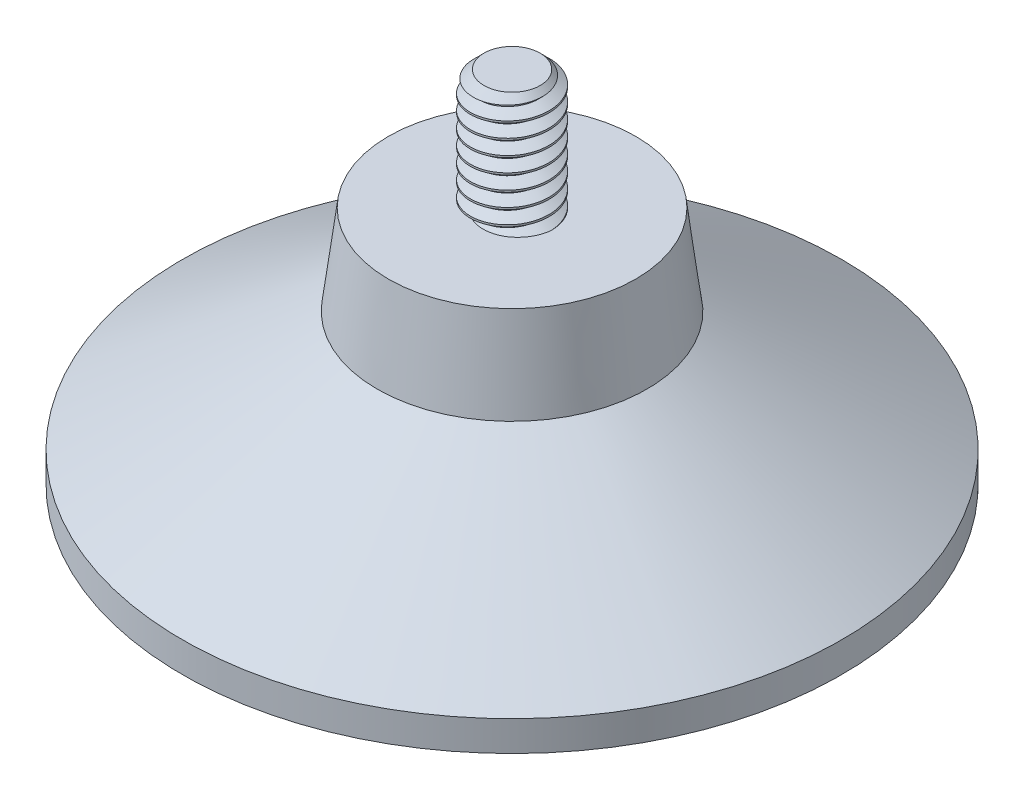
SolidWorks part; units mm, degrees
ref_plane "Front" through (0, 0, 0) normal (0, 0, 1) x (1, 0, 0)
ref_plane "Top" through (0, 0, 0) normal (0, 1, 0) x (1, 0, 0)
ref_plane "Right" through (0, 0, 0) normal (1, 0, 0) x (0, 0, -1)
sketch "Sketch1" plane through (0, 0, 0) normal (0, 0, 1) x (1, 0, 0)
  line L0 (-17.4625, 0) -> (17.4625, 0) construction
  line L1 (0, 0) -> (0, 19.05) construction
  line L2 (17.4625, 0) -> (17.4625, 1.6002) construction
  line L3 (6.5532, 12.7) -> (7.1501, 7.9502) construction
  line L4 (6.5532, 12.7) -> (-6.5532, 12.7) construction
  line L5 (-6.5532, 12.7) -> (-7.1501, 7.9502) construction
  line L6 (-17.4625, 0) -> (-17.4625, 1.6002) construction
  line L7 (-2.0828, 19.05) -> (2.0828, 19.05) construction
  line L8 (2.0828, 19.05) -> (2.0828, 12.7)
  line L9 (-2.0828, 19.05) -> (-2.0828, 12.7) construction
  line L10 (-7.1501, 7.9502) -> (7.1501, 7.9502) construction
  line L11 (-3.175, 6.35) -> (-4.3246, 5.2552) construction
  line L12 (2.0828, 12.7) -> (0, 12.7)
  line L13 (0, 12.7) -> (0, 19.05)
  line L14 (0, 19.05) -> (2.0828, 19.05)
  line L15 (-7.1501, 7.9502) -> (-17.4625, 1.6002) construction
  line L16 (7.1501, 7.9502) -> (17.4625, 1.6002) construction
  line L17 (-3.175, 6.35) -> (3.175, 6.35) construction
  line L19 (3.175, 6.35) -> (4.3246, 5.2552) construction
  arc A2 (4.3246, 5.2552) -> (17.4625, 0) centre (17.4625, 19.05) ccw construction
  arc A3 (-4.3246, 5.2552) -> (-17.4625, 0) centre (-17.4625, 19.05) cw construction
  point P7 (0, 12.7)
  point P18 (0, 19.05)
  point P19 (0, 7.9502)
  point P22 (0, 6.35)
  dimension "D3" = 19.05
  dimension "D1" = 6.35
  dimension "D2" = 6.35
revolve "Revolve1" add sketch "Sketch1" angle 360 mid plane about L13
sketch "Sketch2" plane through (0, 19.05, 0) normal (0, 1, 0) x (1, 0, 0)
  circle A1 centre (0, 0) radius 2.0828
  circle A2 centre (0, 0) radius 2.0828
  dimension "D1" = 0
curve "Helix/Spiral1" pitch 0.7937 height 7.1437 turns 9 parameters "Thread Pitch"=0.7937
chamfer "Chamfer1" distance 0.5953 angle 45 1 edges at (0, 19.05, -2.0828)
sketch "Sketch4" plane through (0, 0, 0) normal (0, 0, 1) x (1, 0, 0)
  line L0 (2.0828, 19.05) -> (2.0828, 19.7445) construction
  line L1 (2.0828, 19.7445) -> (1.5672, 19.4469) construction
  line L2 (1.5672, 19.4469) -> (1.5672, 19.3477)
  line L3 (1.5672, 19.3477) -> (2.0828, 19.05) construction
  line L4 (1.5672, 19.3973) -> (2.0828, 19.3973) construction
  line L5 (1.825, 19.1988) -> (1.825, 19.5957) construction
  line L6 (1.5672, 19.4469) -> (2.1082, 19.7592)
  line L7 (1.5672, 19.3477) -> (2.1082, 19.0353)
  line L8 (2.1082, 19.0353) -> (2.1082, 19.7592)
  dimension "D1" = 0.0992
  dimension "D2" = 0.3969
  dimension "D3" = 0.0254
  dimension "D4" = 60
sweep "Cut-Sweep1" cut profiles "Sketch4" path "Helix/Spiral1" align with end faces yes
sketch "Sketch5" plane through (0, 0, 0) normal (0, 0, 1) x (1, 0, 0)
  line L0 (0, 6.35) -> (0, 12.7)
  line L2 (-3.175, 6.35) -> (3.175, 6.35) construction
  line L4 (0, 12.7) -> (6.5532, 12.7)
  line L5 (6.5532, 12.7) -> (7.1501, 7.9502)
  line L6 (7.1501, 7.9502) -> (17.4625, 1.6002)
  line L7 (17.4625, 1.6002) -> (17.4625, 0)
  line L8 (0, 6.35) -> (3.175, 6.35)
  line L9 (3.175, 6.35) -> (4.3246, 5.2552)
  arc A2 (4.3246, 5.2552) -> (17.4625, 0) centre (17.4625, 19.05) ccw construction
  arc A3 (4.3246, 5.2552) -> (17.4625, 0) centre (17.4625, 19.05) ccw
revolve "Revolve2" add sketch "Sketch5" angle 360 mid plane about L1
equation "\"D3@Helix/Spiral1\" = \"Thread Lg@Sketch1\" + \"Thread Pitch@Helix/Spiral1\""
equation "\"D1@Chamfer1\" = \"Thread Pitch@Helix/Spiral1\" * .75"
equation "\"D1@Sketch4\" = \"Thread Pitch@Helix/Spiral1\" * .125"
equation "\"D2@Sketch4\" = \"Thread Pitch@Helix/Spiral1\" * .5"
